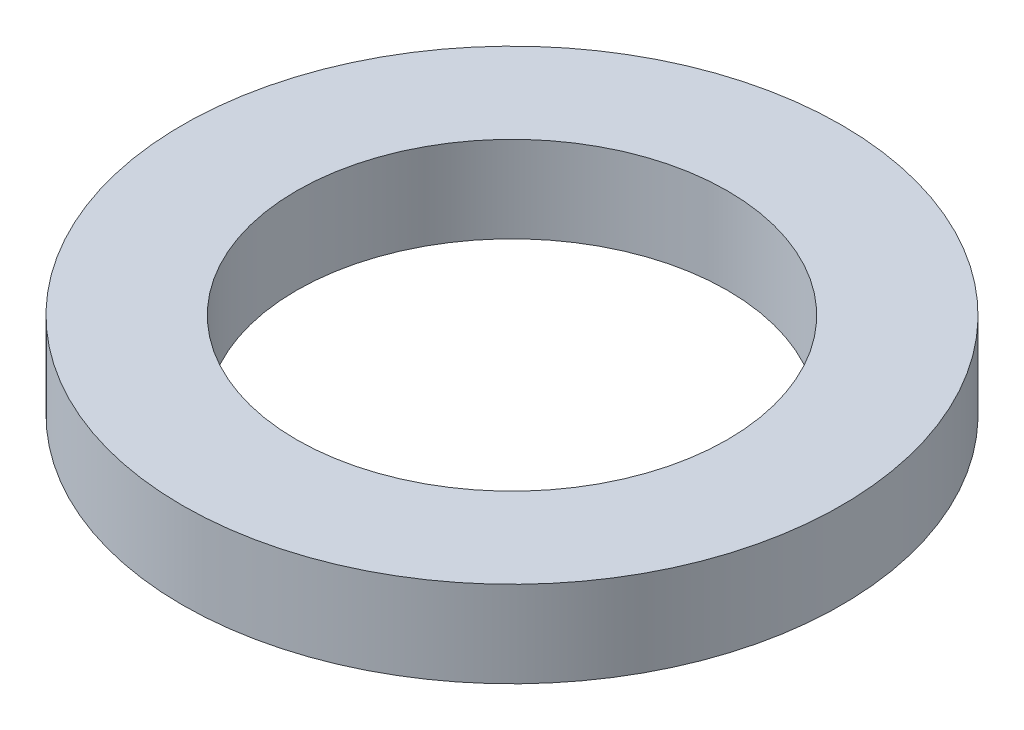
SolidWorks part; units mm, degrees
ref_plane "Front Plane" through (0, 0, 0) normal (0, 0, 1) x (1, 0, 0)
ref_plane "Top Plane" through (0, 0, 0) normal (0, 1, 0) x (1, 0, 0)
ref_plane "Right Plane" through (0, 0, 0) normal (1, 0, 0) x (0, 0, -1)
sketch "Sketch1" plane through (0, 0, 0) normal (0, 1, 0) x (1, 0, 0)
  circle A0 centre (0, 0) radius 65
  dimension "FLANGE_OD" = 130
extrude "Boss-Extrude1" add sketch "Sketch1" along normal blind 17
sketch "Sketch2" plane through (0, 0, 0) normal (0, 1, 0) x (1, 0, 0)
  circle A0 centre (0, 0) radius 42.5
  dimension "BORE_D" = 85
extrude "Cut-Extrude1" cut sketch "Sketch2" along normal through all
sketch "Sketch3" plane through (0, 17, 0) normal (0, 1, 0) x (1, 0, 0)
  circle A0 centre (0, 0) radius 28.3714 construction
  circle A1 centre (-28.3714, 0) radius 1.5734
  dimension "BOLT_D" = 3.1468
  dimension "BOLT_PCD" = 56.7427
extrude "Cut-Extrude2" cut sketch "Sketch3" against normal blind 11.023 rebuild error yes
pattern_circular "CirPattern1" count 6 over 360 rebuild error yes
